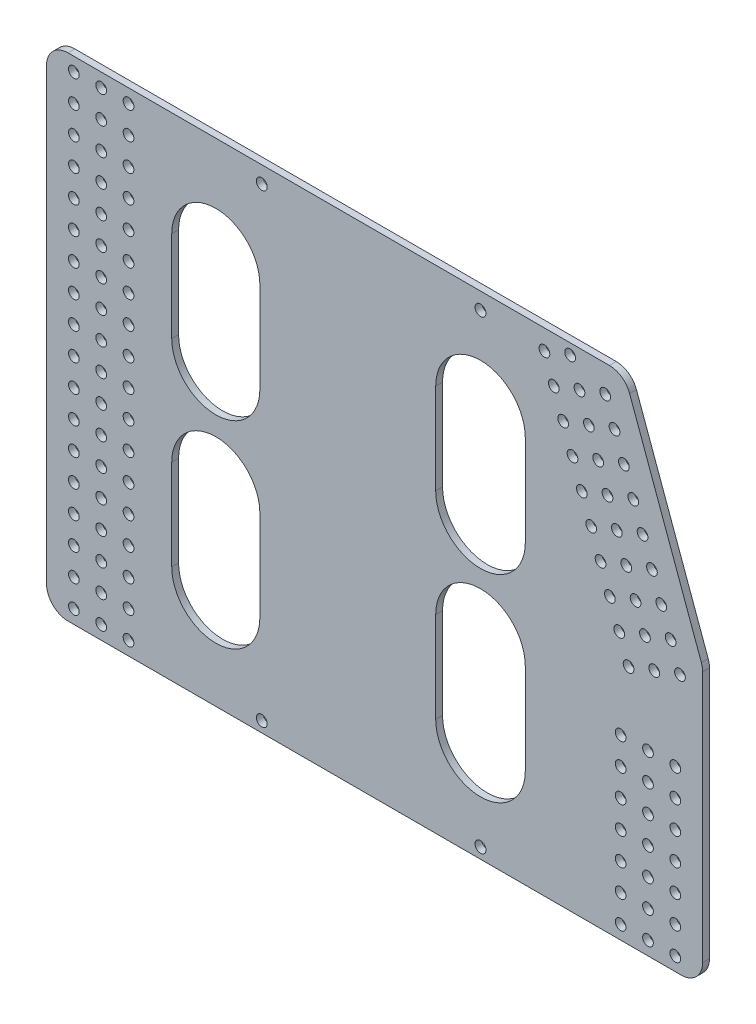
SolidWorks part; units mm, degrees
ref_plane "Front Plane" through (0, 0, 0) normal (0, 0, 1) x (1, 0, 0)
ref_plane "Top Plane" through (0, 0, 0) normal (0, 1, 0) x (1, 0, 0)
ref_plane "Right Plane" through (0, 0, 0) normal (1, 0, 0) x (0, 0, -1)
sketch "Sketch3" plane through (0, 0, 0) normal (0, 0, 1) x (1, 0, 0)
  line L0 (-62.0347, 275.0603) -> (206.4353, 275.0603)
  line L1 (204.6653, 90.9103) -> (204.6653, 78.2103) construction
  line L3 (206.4353, 275.0603) -> (242.7653, 175.2445)
  line L4 (242.7653, 175.2445) -> (242.7653, 46.4603)
  line L6 (242.7653, 46.4603) -> (-62.0347, 46.4603)
  line L7 (-62.0347, 46.4603) -> (-62.0347, 275.0603)
  line L8 (-49.3347, 268.7103) -> (-36.6347, 268.7103) construction
  line L9 (-49.3347, 268.7103) -> (-49.3347, 256.0103) construction
  line L10 (105.1393, -854.8604) -> (105.1393, 49145.1396) construction
  line L11 (169.2687, 265.7779) -> (173.6123, 253.8438) construction
  line L12 (204.6653, 129.0103) -> (204.6653, 116.3103) construction
  line L13 (23.6016, 116.2566) -> (23.6016, 141.6566) construction
  line L14 (23.6016, 185.8526) -> (23.6016, 211.2526) construction
  line L15 (-894.8607, 145.1396) -> (49105.1393, 145.1396) construction
  circle A0 centre (123.2241, 114.6088) radius 2.4892
  circle A1 centre (87.0545, 114.6088) radius 2.4892
  circle A2 centre (-49.3347, 268.7103) radius 2.4892
  circle A3 centre (-49.3347, 90.9103) radius 2.4892
  circle A4 centre (-36.6347, 268.7103) radius 2.4892
  circle A5 centre (-23.9347, 268.7103) radius 2.4892
  circle A6 centre (-36.6347, 256.0103) radius 2.4892
  circle A7 centre (-23.9347, 256.0103) radius 2.4892
  circle A8 centre (-36.6347, 243.3103) radius 2.4892
  circle A9 centre (-23.9347, 243.3103) radius 2.4892
  circle A10 centre (-36.6347, 230.6103) radius 2.4892
  circle A11 centre (-23.9347, 230.6103) radius 2.4892
  circle A12 centre (-36.6347, 217.9103) radius 2.4892
  circle A13 centre (-23.9347, 217.9103) radius 2.4892
  circle A14 centre (-36.6347, 205.2103) radius 2.4892
  circle A15 centre (-23.9347, 205.2103) radius 2.4892
  circle A16 centre (-36.6347, 192.5103) radius 2.4892
  circle A17 centre (-23.9347, 192.5103) radius 2.4892
  circle A18 centre (-36.6347, 179.8103) radius 2.4892
  circle A19 centre (-23.9347, 179.8103) radius 2.4892
  circle A20 centre (-36.6347, 167.1103) radius 2.4892
  circle A21 centre (-23.9347, 167.1103) radius 2.4892
  circle A22 centre (-36.6347, 154.4103) radius 2.4892
  circle A23 centre (-23.9347, 154.4103) radius 2.4892
  circle A24 centre (-36.6347, 141.7103) radius 2.4892
  circle A25 centre (-23.9347, 141.7103) radius 2.4892
  circle A26 centre (-36.6347, 129.0103) radius 2.4892
  circle A27 centre (-23.9347, 129.0103) radius 2.4892
  circle A28 centre (-36.6347, 116.3103) radius 2.4892
  circle A29 centre (-23.9347, 116.3103) radius 2.4892
  circle A30 centre (-36.6347, 103.6103) radius 2.4892
  circle A31 centre (-23.9347, 103.6103) radius 2.4892
  circle A32 centre (-36.6347, 90.9103) radius 2.4892
  circle A33 centre (-23.9347, 90.9103) radius 2.4892
  circle A34 centre (-49.3347, 256.0103) radius 2.4892
  circle A35 centre (-49.3347, 243.3103) radius 2.4892
  circle A36 centre (-49.3347, 230.6103) radius 2.4892
  circle A37 centre (-49.3347, 217.9103) radius 2.4892
  circle A38 centre (-49.3347, 205.2103) radius 2.4892
  circle A39 centre (-49.3347, 192.5103) radius 2.4892
  circle A40 centre (-49.3347, 179.8103) radius 2.4892
  circle A41 centre (-49.3347, 167.1103) radius 2.4892
  circle A42 centre (-49.3347, 154.4103) radius 2.4892
  circle A43 centre (-49.3347, 141.7103) radius 2.4892
  circle A44 centre (-49.3347, 129.0103) radius 2.4892
  circle A45 centre (-49.3347, 116.3103) radius 2.4892
  circle A46 centre (-49.3347, 103.6103) radius 2.4892
  circle A47 centre (-49.3347, 90.9103) radius 2.4892
  circle A48 centre (169.2687, 265.7779) radius 2.4892
  circle A49 centre (181.2028, 270.1215) radius 2.4892
  circle A50 centre (197.4805, 262.5311) radius 2.4892
  circle A51 centre (173.6123, 253.8438) radius 2.4892
  circle A52 centre (185.5464, 258.1874) radius 2.4892
  circle A53 centre (201.8242, 250.597) radius 2.4892
  circle A54 centre (177.956, 241.9097) radius 2.4892
  circle A55 centre (189.8901, 246.2533) radius 2.4892
  circle A56 centre (206.1678, 238.6629) radius 2.4892
  circle A57 centre (182.2996, 229.9756) radius 2.4892
  circle A58 centre (194.2337, 234.3192) radius 2.4892
  circle A59 centre (210.5115, 226.7288) radius 2.4892
  circle A60 centre (186.6433, 218.0415) radius 2.4892
  circle A61 centre (198.5774, 222.3851) radius 2.4892
  circle A62 centre (214.8551, 214.7947) radius 2.4892
  circle A63 centre (190.9869, 206.1074) radius 2.4892
  circle A64 centre (202.921, 210.451) radius 2.4892
  circle A65 centre (219.1988, 202.8606) radius 2.4892
  circle A66 centre (195.3306, 194.1733) radius 2.4892
  circle A67 centre (207.2647, 198.5169) radius 2.4892
  circle A68 centre (223.5424, 190.9265) radius 2.4892
  circle A69 centre (199.6743, 182.2392) radius 2.4892
  circle A70 centre (211.6083, 186.5828) radius 2.4892
  circle A71 centre (227.8861, 178.9924) radius 2.4892
  circle A72 centre (204.0179, 170.3051) radius 2.4892
  circle A73 centre (215.952, 174.6488) radius 2.4892
  circle A74 centre (232.2298, 167.0583) radius 2.4892
  circle A75 centre (208.3616, 158.371) radius 2.4892
  circle A76 centre (220.2957, 162.7147) radius 2.4892
  circle A78 centre (236.5734, 155.1242) radius 2.4892 [skipped]
  circle A79 centre (204.6653, 129.0103) radius 2.4892
  circle A80 centre (217.3653, 129.0103) radius 2.4892
  circle A81 centre (230.0653, 129.0103) radius 2.4892
  circle A82 centre (204.6653, 116.3103) radius 2.4892
  circle A83 centre (217.3653, 116.3103) radius 2.4892
  circle A84 centre (230.0653, 116.3103) radius 2.4892
  circle A85 centre (204.6653, 103.6103) radius 2.4892
  circle A86 centre (217.3653, 103.6103) radius 2.4892
  circle A87 centre (230.0653, 103.6103) radius 2.4892
  circle A88 centre (204.6653, 90.9103) radius 2.4892
  circle A89 centre (217.3653, 90.9103) radius 2.4892
  circle A90 centre (230.0653, 90.9103) radius 2.4892
  circle A91 centre (23.6016, 185.8526) radius 14.2875
  circle A92 centre (52.1422, 151.0564) radius 14.2875
  circle A93 centre (23.6016, 116.2566) radius 14.2875
  circle A94 centre (105.1393, 145.1396) radius 14.2875
  circle A95 centre (104.9447, 224.8273) radius 14.2875
  circle A96 centre (144.1424, 181.3926) radius 14.2875
  circle A99 centre (85.284, 241.0108) radius 2.4892
  circle A100 centre (23.6016, 141.6566) radius 2.4892
  circle A101 centre (45.5987, 128.9566) radius 2.4892
  circle A102 centre (45.5987, 103.5566) radius 2.4892
  circle A103 centre (23.6016, 90.8566) radius 2.4892
  circle A104 centre (1.6046, 103.5566) radius 2.4892
  circle A105 centre (1.6046, 128.9566) radius 2.4892
  circle A106 centre (23.6016, 211.2526) radius 2.4892
  circle A107 centre (45.5987, 198.5526) radius 2.4892
  circle A108 centre (45.5987, 173.1526) radius 2.4892
  circle A109 centre (23.6016, 160.4526) radius 2.4892
  circle A110 centre (1.6046, 173.1526) radius 2.4892
  circle A111 centre (1.6046, 198.5526) radius 2.4892
  circle A112 centre (123.2241, 175.6704) radius 2.4892
  circle A113 centre (87.0545, 175.6704) radius 2.4892
  circle A116 centre (124.6065, 208.849) radius 2.4892
  circle A117 centre (-49.3347, 78.2103) radius 2.4892
  circle A118 centre (-36.6347, 78.2103) radius 2.4892
  circle A119 centre (-23.9347, 78.2103) radius 2.4892
  circle A120 centre (-49.3347, 65.5103) radius 2.4892
  circle A121 centre (-36.6347, 65.5103) radius 2.4892
  circle A122 centre (-23.9347, 65.5103) radius 2.4892
  circle A123 centre (-49.3347, 52.8103) radius 2.4892
  circle A124 centre (-36.6347, 52.8103) radius 2.4892
  circle A125 centre (-23.9347, 52.8103) radius 2.4892
  circle A126 centre (204.6653, 78.2103) radius 2.4892
  circle A127 centre (217.3653, 78.2103) radius 2.4892
  circle A128 centre (230.0653, 78.2103) radius 2.4892
  circle A129 centre (204.6653, 65.5103) radius 2.4892
  circle A130 centre (217.3653, 65.5103) radius 2.4892
  circle A131 centre (230.0653, 65.5103) radius 2.4892
  circle A132 centre (204.6653, 52.8103) radius 2.4892
  circle A133 centre (217.3653, 52.8103) radius 2.4892
  circle A134 centre (230.0653, 52.8103) radius 2.4892
  dimension "D1" = 4.9784
  dimension "D2" = 6.35
  dimension "D10" = 4.9784
  dimension "D11" = 4.9784
  dimension "D12" = 4.9784
  dimension "D15" = 4.9784
  dimension "D16" = 4.9784
  dimension "D17" = 4.9784
  dimension "D20" = 4.9784
  dimension "D21" = 28.575
  dimension "D22" = 28.575
  dimension "D23" = 28.575
  dimension "D24" = 28.575
  dimension "D25" = 28.575
  dimension "D26" = 28.575
  dimension "D27" = 12.7
  dimension "D28" = 4.9784
  dimension "D32" = 4.9784
  dimension "D35" = 4.9784
  dimension "D38" = 4.9784
  dimension "D5" = 3
  dimension "D7" = 12.7
  dimension "D8" = 12.7
  dimension "D9" = 228.6
  dimension "D14" = 12.7
  dimension "D19" = 12.7
  dimension "D29" = 25.4
  dimension "D31" = 25.4
  dimension "D33" = 6
  dimension "D34" = 25.4
  dimension "D36" = 18.0848
  dimension "D37" = 30.5308
  dimension "D39" = 19.6607
  dimension "D40" = 16.1835
  dimension "D41" = 12.7
  dimension "D42" = 15.9782
  dimension "D43" = 19.6618
  dimension "D6" = 15
  dimension "D13" = 10
  dimension "D18" = 4
  dimension "D30" = 6
extrude "Boss-Extrude3" add sketch "Sketch3" along normal blind 3.175
fillet "Fillet2" radius 10 5 edges at (-62.0347, 275.0603, 1.5875) (-62.0347, 46.4603, 1.5875) (242.7653, 46.4603, 1.5875) (242.7653, 175.2445, 1.5875) (206.4353, 275.0603, 1.5875)
sketch "Sketch5" plane through (0, 0, 3.175) normal (0, 0, 1) x (1, 0, 0)
  circle A0 centre (23.6016, 185.8526) radius 14.2875
  circle A1 centre (23.6016, 211.2526) radius 2.4892
  circle A2 centre (45.5987, 198.5526) radius 2.4892
  circle A3 centre (1.6046, 198.5526) radius 2.4892
  circle A4 centre (1.6046, 173.1526) radius 2.4892
  circle A5 centre (23.6016, 160.4526) radius 2.4892
  circle A6 centre (45.5987, 173.1526) radius 2.4892
  circle A7 centre (23.6016, 116.2566) radius 14.2875
  circle A8 centre (1.6046, 128.9566) radius 2.4892
  circle A9 centre (23.6016, 141.6566) radius 2.4892
  circle A10 centre (45.5987, 128.9566) radius 2.4892
  circle A11 centre (1.6046, 103.5566) radius 2.4892
  circle A12 centre (23.6016, 90.8566) radius 2.4892
  circle A13 centre (45.5987, 103.5566) radius 2.4892
  circle A14 centre (52.1422, 151.0564) radius 14.2875
  circle A15 centre (105.1393, 145.1396) radius 14.2875
  circle A16 centre (87.0545, 114.6088) radius 2.4892
  circle A17 centre (123.2241, 114.6088) radius 2.4892
  circle A18 centre (87.0545, 175.6704) radius 2.4892
  circle A19 centre (123.2241, 175.6704) radius 2.4892
  circle A20 centre (144.1424, 181.3926) radius 14.2875
  circle A21 centre (104.9447, 224.8273) radius 14.2875
  circle A22 centre (124.6065, 208.849) radius 2.4892
  circle A23 centre (85.284, 241.0108) radius 2.4892
extrude "Boss-Extrude5" add sketch "Sketch5" against normal blind 3.175
sketch "Sketch6" plane through (0, 0, 3.175) normal (0, 0, 1) x (1, 0, 0)
  line L0 (16.6029, 184.2341) -> (16.6029, 226.3723) construction
  line L3 (-3.8642, 184.2341) -> (-3.8642, 226.3723)
  line L4 (32.254, 159.3691) -> (143.252, 159.3691) construction
  line L5 (87.753, 159.3691) -> (87.753, 108.5741) construction
  line L6 (37.0701, 184.2341) -> (37.0701, 226.3723)
  line L9 (-62.0347, 265.0603) -> (-62.0347, 56.4603) construction
  line L10 (87.753, 268.0089) -> (87.753, 52.1089) construction
  line L11 (87.753, 159.3691) -> (276.8248, 159.3691) construction
  line L12 (139.5653, 184.2341) -> (139.5653, 226.3723) construction
  line L13 (118.7562, 184.2341) -> (118.7562, 226.3723)
  line L14 (160.3743, 184.2341) -> (160.3743, 226.3723)
  line L15 (139.5653, 134.504) -> (139.5653, 92.3658) construction
  line L16 (118.7562, 134.504) -> (118.7562, 92.3658)
  line L17 (160.3743, 134.504) -> (160.3743, 92.3658)
  line L18 (16.6029, 134.504) -> (16.6029, 92.3658) construction
  line L19 (-3.8642, 134.504) -> (-3.8642, 92.3658)
  line L20 (37.0701, 134.504) -> (37.0701, 92.3658)
  circle A4 centre (37.9653, 267.3191) radius 2.54
  circle A5 centre (139.5653, 267.3191) radius 2.54
  circle A6 centre (139.5653, 51.4191) radius 2.54
  circle A7 centre (37.9653, 51.4191) radius 2.54
  arc A8 (-3.8642, 184.2341) -> (37.0701, 184.2341) centre (16.6029, 184.2341) ccw
  arc A9 (37.0701, 226.3723) -> (-3.8642, 226.3723) centre (16.6029, 226.3723) ccw
  arc A10 (118.7562, 184.2341) -> (160.3743, 184.2341) centre (139.5653, 184.2341) ccw
  arc A11 (160.3743, 226.3723) -> (118.7562, 226.3723) centre (139.5653, 226.3723) ccw
  arc A12 (118.7562, 134.504) -> (160.3743, 134.504) centre (139.5653, 134.504) cw
  arc A13 (160.3743, 92.3658) -> (118.7562, 92.3658) centre (139.5653, 92.3658) cw
  arc A14 (-3.8642, 134.504) -> (37.0701, 134.504) centre (16.6029, 134.504) cw
  arc A15 (37.0701, 92.3658) -> (-3.8642, 92.3658) centre (16.6029, 92.3658) cw
  point P2 (16.6029, 205.3032)
  point P9 (139.5653, 205.3032)
  point P20 (139.5653, 113.4349)
  point P40 (16.6029, 113.4349)
  dimension "D4" = 5.08
  dimension "D5" = 5.08
  dimension "D3" = 110.998
  dimension "D6" = 101.6
  dimension "D7" = 100
  dimension "D8" = 215.9
  dimension "D9" = 215.9
extrude "Cut-Extrude1" cut sketch "Sketch6" against normal blind 3.175
